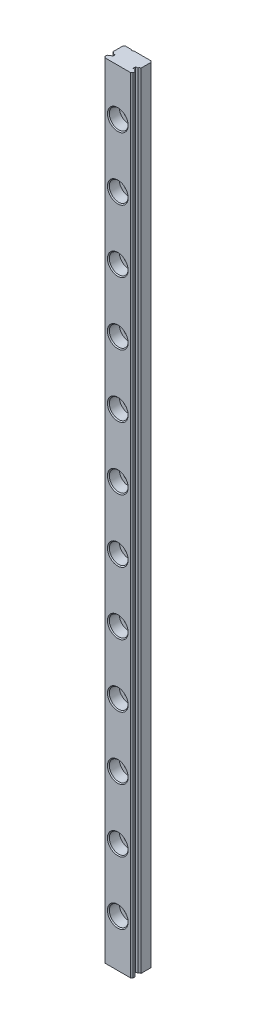
SolidWorks part; units mm, degrees
ref_plane "Horní rovina" through (0, 0, 0) normal (0, 0, 1) x (1, 0, 0)
ref_plane "Přední rovina" through (0, 0, 0) normal (0, 1, 0) x (1, 0, 0)
ref_plane "Pravá rovina" through (0, 0, 0) normal (1, 0, 0) x (0, 0, -1)
sketch "Skica1" plane through (0, 0, 0) normal (0, 1, 0) x (1, 0, 0)
  line L17 (0, -14.9046) -> (0, 0) construction
  line L22 (3.3, -4.5) -> (0, -4.5) construction
  line L23 (-4.1, -6.5) -> (4.1, -6.5)
  line L24 (4.1, -6.5) -> (4.5, -6.1)
  line L25 (4.5, -6.1) -> (4.5, -5.4539)
  line L26 (3.9045, -4.945) -> (3.3, -4.89)
  line L27 (3.3, -4.89) -> (3.3, -4.11)
  line L28 (3.3, -4.11) -> (3.9095, -4.045)
  line L29 (4.5, -3.5461) -> (4.5, -0.4)
  line L30 (4.5, -0.4) -> (4.1, 0)
  line L31 (4.1, 0) -> (-1.4, 0)
  line L32 (-2.2, 0) -> (-4.1, 0)
  line L33 (-4.1, 0) -> (-4.5, -0.4)
  line L34 (-4.5, -0.4) -> (-4.5, -3.5461)
  line L38 (-4.5, -5.4539) -> (-4.5, -6.1)
  line L39 (-4.5, -6.1) -> (-4.1, -6.5)
  line L40 (-3.3, -4.11) -> (-3.9095, -4.045)
  line L41 (-3.3, -4.89) -> (-3.3, -4.11)
  line L42 (-3.9045, -4.945) -> (-3.3, -4.89)
  arc A7 (3.9045, -4.945) -> (4.5, -5.4539) centre (4.8, -4.5) ccw
  arc A8 (4.5, -3.5461) -> (3.9095, -4.045) centre (4.8, -4.5) ccw
  arc A9 (-2.2, 0) -> (-1.4, 0) centre (-1.8, 0.3) ccw
  arc A12 (-4.5, -3.5461) -> (-3.9095, -4.045) centre (-4.8, -4.5) cw
  arc A13 (-3.9045, -4.945) -> (-4.5, -5.4539) centre (-4.8, -4.5) cw
  point P4 (0, -6.5)
  dimension "D7" = 1
  dimension "D19" = 0.5
  dimension "D2" = 8.2
  dimension "D1" = 4.5
  dimension "D4" = 6.5
  dimension "D5" = 0.3
  dimension "D6" = 2
  dimension "D8" = 0.78
  dimension "D9" = 0.9
  dimension "D10" = 1.2
  dimension "D12" = 0.4
  dimension "D13" = 0.4
  dimension "D15" = 0.4
  dimension "D16" = 0.4
  dimension "D17" = 0.3
  dimension "D18" = 1.8
extrude "Delka" add sketch "Skica1" along normal blind 250
hole_wizard "Díra1" positions "Skica3" profile "Skica4" legacy end condition through all
sketch "Skica3" plane through (0, 0, 6.5) normal (0, 0, 1) x (1, 0, 0)
  point P0 (0, 15)
  point P2 (0, 15)
  dimension "D1" = 15
sketch "Skica4" plane through (0, 15, 6.5) normal (1, 0, 0) x (0, -1, 0)
  line L0 (0, 0) -> (0, 6.6576)
  line L1 (0, 6.6576) -> (1.75, 6.6576)
  line L2 (1.75, 6.6576) -> (1.75, 3.5)
  line L3 (1.75, 3.5) -> (3, 3.5)
  line L4 (3, 3.5) -> (3, 0)
  line L5 (3, 0) -> (0, 0)
  line L6 (0, 110) -> (0, -10) construction
  dimension "Průměr" = 3.5
  dimension "Hloubka" = 6.6576
  dimension "Průměr válc. zahloubení" = 6
  dimension "Hloubka válc. zahloubení" = 3.5
chamfer "Zkosení1" distance 0.3 angle 45 2 edges at (1.75, 15, 0) (3, 15, 6.5)
pattern_linear "LinPole1" count 12 spacing 20 along (0, 1, 0) of "Díra1", "Zkosení1"
equation "\"P\"= 20mm"
equation "\"Emin\"= 8mm"
equation "\"Emax\"= 20mm"
equation "\"Hc\"= round (  ( \"D1@Delka\" - 2 * \"Emin\" )  / \"P\" ) "
equation "\"E\"= ( \"L\" - ( ( \"Hc\" - 1 ) * \"P\" ) ) / 2"
equation "\"L\"= 250"
equation "\"D1@Delka\" = \"L\""
equation "\"D1@LinPole1\"= \"Hc\""
equation "\"D3@LinPole1\"= \"P\""
equation "\"D1@Skica3\"= \"E\""
equation "\"Přidat vysunutím1\"= \"L\""
equation "\"Delka\"= \"L\""
equation "\"D13@Skica1\"=\"D12@Skica1\""
equation "\"D15@Skica1\"=\"D12@Skica1\""
equation "\"D16@Skica1\"=\"D12@Skica1\""
